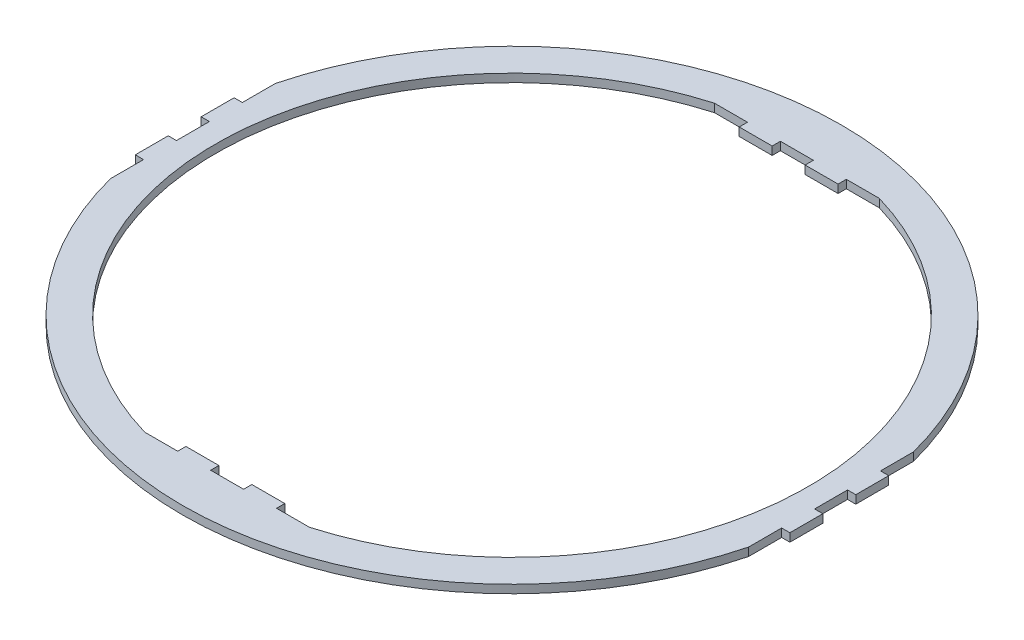
SolidWorks part; units mm, degrees
ref_plane "Front Plane" through (0, 0, 0) normal (0, 0, 1) x (1, 0, 0)
ref_plane "Top Plane" through (0, 0, 0) normal (0, 1, 0) x (1, 0, 0)
ref_plane "Right Plane" through (0, 0, 0) normal (1, 0, 0) x (0, 0, -1)
sketch "Sketch1" plane through (0, 0, 0) normal (0, 1, 0) x (1, 0, 0)
  line L48 (-31.75, 109.8018) -> (-19.05, 109.8018)
  line L53 (-19.05, 109.8018) -> (-19.05, 106.6268)
  line L54 (-19.05, 106.6268) -> (-6.35, 106.6268)
  line L55 (-6.35, 106.6268) -> (-6.35, 109.8018)
  line L56 (-6.35, 109.8018) -> (6.35, 109.8018)
  line L57 (6.35, 109.8018) -> (6.35, 106.6268)
  line L58 (6.35, 106.6268) -> (19.05, 106.6268)
  line L59 (19.05, 106.6268) -> (19.05, 109.8018)
  line L60 (19.05, 109.8018) -> (31.75, 109.8018)
  line L61 (-31.75, -109.8018) -> (-19.05, -109.8018)
  line L62 (-19.05, -109.8018) -> (-19.05, -106.6268)
  line L65 (-6.35, -109.8018) -> (6.35, -109.8018)
  line L66 (6.35, -109.8018) -> (6.35, -106.6268)
  line L67 (6.35, -106.6268) -> (19.05, -106.6268)
  line L68 (19.05, -106.6268) -> (19.05, -109.8018)
  line L69 (19.05, -109.8018) -> (31.75, -109.8018)
  line L70 (-6.35, -109.8018) -> (-6.35, -106.6268)
  line L71 (-6.35, -106.6268) -> (-19.05, -106.6268)
  line L72 (122.9672, -31.75) -> (122.9672, -19.05)
  line L73 (122.9672, -19.05) -> (126.1422, -19.05)
  line L74 (126.1422, -19.05) -> (126.1422, -6.35)
  line L75 (126.1422, -6.35) -> (122.9672, -6.35)
  line L76 (122.9672, -6.35) -> (122.9672, 6.35)
  line L77 (122.9672, 6.35) -> (126.1422, 6.35)
  line L78 (126.1422, 6.35) -> (126.1422, 19.05)
  line L79 (126.1422, 19.05) -> (122.9672, 19.05)
  line L80 (122.9672, 19.05) -> (122.9672, 31.75)
  line L95 (-122.9672, 31.75) -> (-122.9672, 19.05)
  line L96 (-122.9672, 19.05) -> (-126.1422, 19.05)
  line L97 (-126.1422, 19.05) -> (-126.1422, 6.35)
  line L98 (-126.1422, 6.35) -> (-122.9672, 6.35)
  line L99 (-122.9672, 6.35) -> (-122.9672, -6.35)
  line L100 (-122.9672, -6.35) -> (-126.1422, -6.35)
  line L101 (-126.1422, -6.35) -> (-126.1422, -19.05)
  line L102 (-126.1422, -19.05) -> (-122.9672, -19.05)
  line L103 (-122.9672, -19.05) -> (-122.9672, -31.75)
  arc A16 (-31.75, -109.8018) -> (-31.75, 109.8018) centre (0, 0) cw
  arc A17 (31.75, 109.8018) -> (31.75, -109.8018) centre (0, 0) cw
  arc A19 (-122.9672, 31.75) -> (122.9672, 31.75) centre (0, 0) cw
  arc A20 (122.9672, -31.75) -> (-122.9672, -31.75) centre (0, 0) cw
  dimension "D3" = 12.7
  dimension "D7" = 12.7
  dimension "D12" = 12.7
  dimension "D6" = 3.175
  dimension "D8" = 12.7
  dimension "D5" = 12.7
  dimension "D1" = 114.3
  dimension "D2" = 12.7
  dimension "D18" = 127
  dimension "D19" = 127
  dimension "D4" = 12.7
  dimension "D9" = 12.7
  dimension "D10" = 3.175
  dimension "D11" = 3.175
  dimension "D13" = 12.7
  dimension "D14" = 12.7
  dimension "D15" = 12.7
  dimension "D16" = 12.7
  dimension "D17" = 3.175
extrude "Boss-Extrude1" add sketch "Sketch1" along normal blind 3.175
